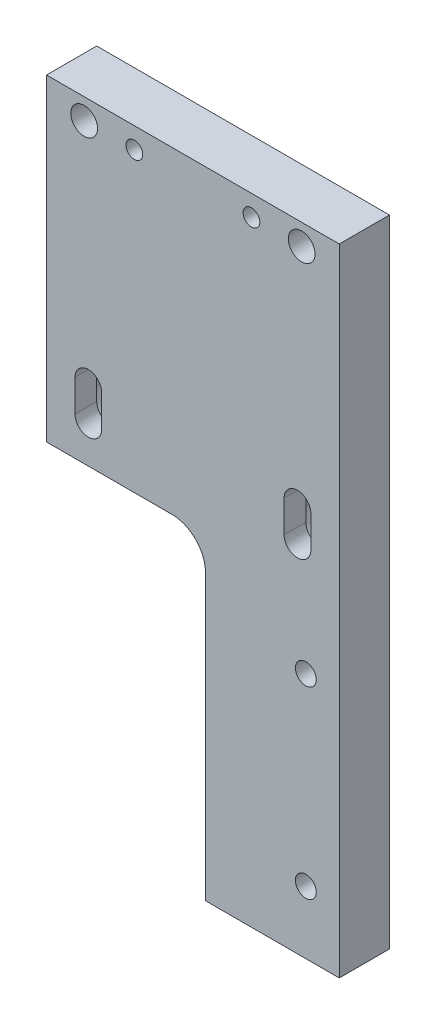
SolidWorks part; units mm, degrees
ref_plane "Front Plane" through (0, 0, 0) normal (0, 0, 1) x (1, 0, 0)
ref_plane "Top Plane" through (0, 0, 0) normal (0, 1, 0) x (1, 0, 0)
ref_plane "Right Plane" through (0, 0, 0) normal (1, 0, 0) x (0, 0, -1)
sketch "Sketch1" plane through (0, 0, 0) normal (0, 1, 0) x (1, 0, 0)
  line L1 (0, 0) -> (35, 0)
  line L2 (0, 0) -> (0, 6)
  line L3 (0, 6) -> (35, 6)
  line L4 (35, 0) -> (35, 6)
  dimension "D1" = 6
  dimension "D2" = 35
extrude "Boss-Extrude1" add sketch "Sketch1" along normal blind 76
sketch "Sketch2" plane through (0, 0, 0) normal (0, 0, 1) x (1, 0, 0)
  line L0 (17.5, 76) -> (17.5, 0) construction
  line L1 (0, 76) -> (35, 76) construction
  line L2 (0, 0) -> (35, 0) construction
  circle A0 centre (4.5, 73.5) radius 1.6
  circle A1 centre (30.5, 73.5) radius 1.6
  dimension "D3" = 3.2
  dimension "D1" = 2.5
  dimension "D2" = 2.5
  dimension "D4" = 13
  dimension "D5" = 13
extrude "Cut-Extrude1" cut sketch "Sketch2" against normal through all
sketch "Sketch3" plane through (0, 0, 0) normal (0, 0, 1) x (1, 0, 0)
  line L0 (17.5, 76) -> (17.5, 0) construction
  line L1 (0, 76) -> (35, 76) construction
  line L2 (0, 0) -> (35, 0) construction
  circle A0 centre (10.5, 73.5) radius 1
  circle A1 centre (24.5, 73.5) radius 1
  dimension "D5" = 2
  dimension "D1" = 7
  dimension "D2" = 7
  dimension "D3" = 2.5
  dimension "D4" = 2.5
extrude "Cut-Extrude2" cut sketch "Sketch3" against normal blind 4
hole_wizard "CBORE SLOT for M3 Hex Socket Head Cap Screw1" positions "Sketch4" profile "Sketch6" size "M3" standard "DIN" slot yes end condition through all
sketch "Sketch4" plane through (0, 0, -6) normal (0, 0, -1) x (-1, 0, 0)
  line L0 (-30, 41) -> (-30, 48) construction
  line L1 (-35, 76) -> (-35, 0) construction
  line L3 (0, 76) -> (0, 0) construction
  line L4 (-35, 76) -> (0, 76) construction
  point P0 (-30, 44.5)
  point P4 (-5, 44.5)
  dimension "D1" = 7
  dimension "D2" = 5
  dimension "D3" = 31.5
  dimension "D4" = 31.5
  dimension "D5" = 5
sketch "Sketch6" plane through (30, 44.5, -6) normal (1, 0, 0) x (0, 1, 0)
  line L0 (0, 0) -> (0, 6)
  line L1 (0, 6) -> (1.6, 6)
  line L3 (1.6, 6) -> (1.6, 3.4)
  line L4 (1.6, 3.4) -> (3.25, 3.4)
  line L5 (3.25, 3.4) -> (3.25, 0)
  line L7 (3.25, 0) -> (0, 0)
  line L11 (0, -6.35) -> (0, 107.95) construction
  dimension "Thru Hole Dia." = 3.2
  dimension "Thru Hole Depth" = 6
  dimension "C'Bore Dia." = 6.5
  dimension "C'Bore Depth" = 3.4
ref_plane "Plane1" through (17.5, 0, 0) normal (1, 0, 0) x (0, 0, -1)
sketch "Sketch7" plane through (0, 0, -6) normal (0, 0, -1) x (-1, 0, 0)
  line L0 (0, 0) -> (-19, 0)
  line L6 (-35, 0) -> (0, 0) construction
  line L8 (0, 76) -> (0, 0) construction
  line L9 (0, 38) -> (0, 0)
  line L10 (-19, 0) -> (-19, 34)
  line L11 (-15, 38) -> (0, 38)
  arc A0 (-19, 34) -> (-15, 38) centre (-15, 34) cw
  dimension "D3" = 4
  dimension "D1" = 38
  dimension "D2" = 16
extrude "Cut-Extrude3" cut sketch "Sketch7" against normal through all
sketch "Sketch8" plane through (0, 0, -6) normal (0, 0, -1) x (-1, 0, 0)
  line L0 (-35, 18.5) -> (-19, 18.5) construction
  line L1 (-35, 76) -> (-35, 0) construction
  line L3 (-35, 0) -> (-19, 0) construction
  line L4 (-19, 34) -> (-19, 0) construction
  circle A0 centre (-31, 7.5) radius 1.25
  circle A2 centre (-31, 29.5) radius 1.25
  dimension "D3" = 2.5
  dimension "D1" = 18.5
  dimension "D4" = 11
  dimension "D5" = 4
extrude "Cut-Extrude4" cut sketch "Sketch8" against normal through all
